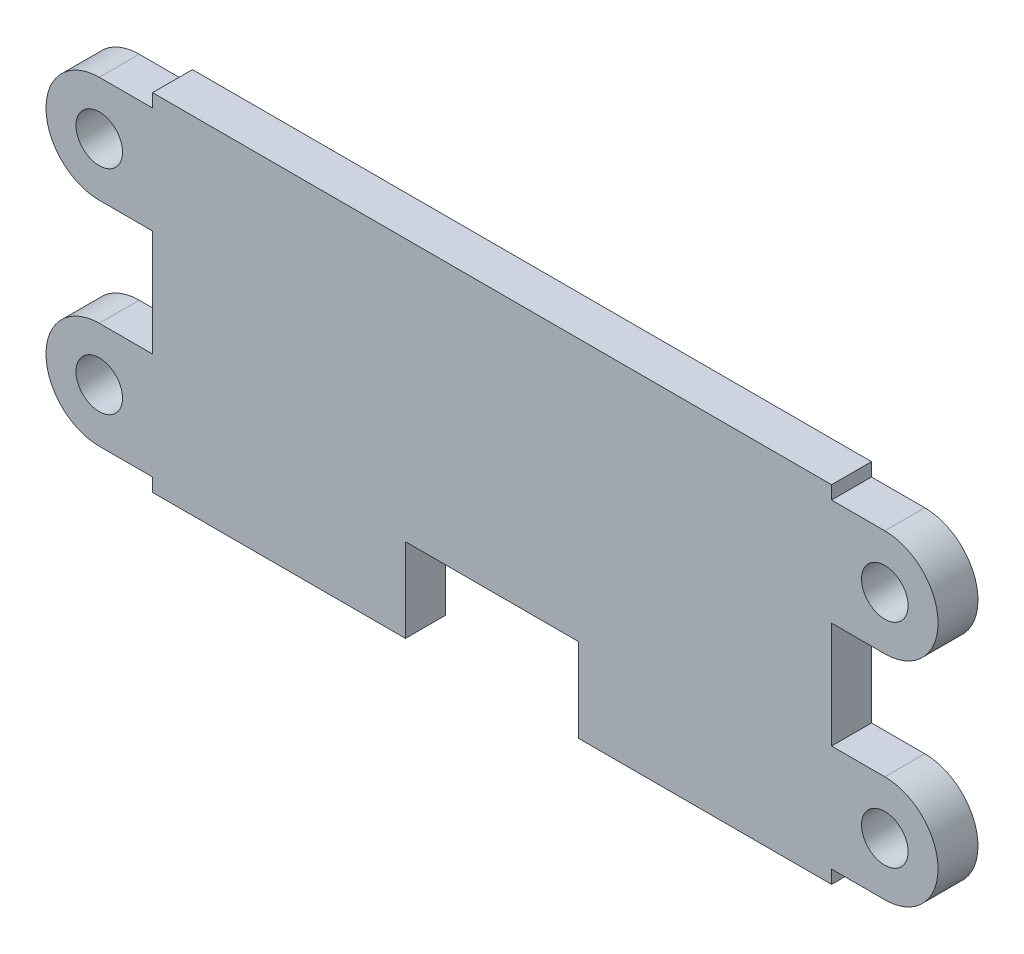
SolidWorks part; units mm, degrees
ref_plane "Ebene vorne" through (0, 0, 0) normal (0, 0, 1) x (1, 0, 0)
ref_plane "Ebene oben" through (0, 0, 0) normal (0, 1, 0) x (1, 0, 0)
ref_plane "Ebene rechts" through (0, 0, 0) normal (1, 0, 0) x (0, 0, -1)
sketch "Skizze1" plane through (0, 0, 0) normal (0, 0, 1) x (1, 0, 0)
  line L16 (-551.7525, 213.3432) -> (-551.7525, 212.3432)
  line L17 (-551.7525, 212.3432) -> (-555.7525, 212.3432)
  line L18 (-555.7525, 204.3432) -> (-551.7525, 204.3432)
  line L19 (-551.7525, 204.3432) -> (-551.7525, 196.3432)
  line L20 (-551.7525, 196.3432) -> (-555.7525, 196.3432)
  line L21 (-555.7525, 188.3432) -> (-551.7525, 188.3432)
  line L22 (-551.7525, 188.3432) -> (-551.7525, 187.3432)
  line L23 (-551.7525, 187.3432) -> (-532.7525, 187.3432)
  line L24 (-500.7525, 187.3432) -> (-500.7525, 188.3432)
  line L25 (-500.7525, 188.3432) -> (-496.7525, 188.3432)
  line L26 (-496.7525, 196.3432) -> (-500.7525, 196.3432)
  line L27 (-500.7525, 196.3432) -> (-500.7525, 204.3432)
  line L28 (-500.7525, 204.3432) -> (-496.7525, 204.3432)
  line L29 (-496.7525, 212.3432) -> (-500.7525, 212.3432)
  line L30 (-500.7525, 212.3432) -> (-500.7525, 213.3432)
  line L31 (-500.7525, 213.3432) -> (-551.7525, 213.3432)
  line L32 (-551.7525, 213.3432) -> (-551.7525, 212.3432)
  line L33 (-551.7525, 212.3432) -> (-555.7525, 212.3432)
  line L34 (-555.7525, 204.3432) -> (-551.7525, 204.3432)
  line L35 (-551.7525, 204.3432) -> (-551.7525, 196.3432)
  line L36 (-551.7525, 196.3432) -> (-555.7525, 196.3432)
  line L37 (-555.7525, 188.3432) -> (-551.7525, 188.3432)
  line L38 (-551.7525, 188.3432) -> (-551.7525, 187.3432)
  line L39 (-551.7525, 187.3432) -> (-532.7525, 187.3432)
  line L40 (-500.7525, 187.3432) -> (-500.7525, 188.3432)
  line L41 (-500.7525, 188.3432) -> (-496.7525, 188.3432)
  line L42 (-496.7525, 196.3432) -> (-500.7525, 196.3432)
  line L43 (-500.7525, 196.3432) -> (-500.7525, 204.3432)
  line L44 (-500.7525, 204.3432) -> (-496.7525, 204.3432)
  line L45 (-496.7525, 212.3432) -> (-500.7525, 212.3432)
  line L46 (-500.7525, 212.3432) -> (-500.7525, 213.3432)
  line L47 (-500.7525, 213.3432) -> (-551.7525, 213.3432)
  line L120 (-532.7525, 187.3432) -> (-532.7525, 193.635)
  line L121 (-532.7525, 193.635) -> (-519.7525, 193.635)
  line L122 (-519.7525, 193.635) -> (-519.7525, 187.3432)
  line L128 (-502.7525, 189.3432) -> (-519.7525, 189.3432)
  line L130 (-519.7525, 189.3432) -> (-519.7525, 187.3432)
  line L132 (-519.7525, 187.3432) -> (-500.7525, 187.3432)
  line L133 (-519.7525, 187.3432) -> (-500.7525, 187.3432)
  line L134 (-532.7525, 187.3432) -> (-532.7525, 189.3432)
  line L136 (-532.7525, 189.3432) -> (-549.7525, 189.3432)
  line L138 (-549.7525, 189.3432) -> (-549.7525, 211.3432)
  line L140 (-549.7525, 211.3432) -> (-502.7525, 211.3432)
  line L142 (-502.7525, 211.3432) -> (-502.7525, 189.3432)
  arc A4 (-555.7525, 212.3432) -> (-555.7525, 204.3432) centre (-555.7525, 208.3432) ccw
  arc A5 (-555.7525, 196.3432) -> (-555.7525, 188.3432) centre (-555.7525, 192.3432) ccw
  arc A6 (-496.7525, 188.3432) -> (-496.7525, 196.3432) centre (-496.7525, 192.3432) ccw
  arc A7 (-496.7525, 204.3432) -> (-496.7525, 212.3432) centre (-496.7525, 208.3432) ccw
  arc A8 (-555.7525, 212.3432) -> (-555.7525, 204.3432) centre (-555.7525, 208.3432) ccw
  arc A9 (-555.7525, 196.3432) -> (-555.7525, 188.3432) centre (-555.7525, 192.3432) ccw
  arc A10 (-496.7525, 188.3432) -> (-496.7525, 196.3432) centre (-496.7525, 192.3432) ccw
  arc A11 (-496.7525, 204.3432) -> (-496.7525, 212.3432) centre (-496.7525, 208.3432) ccw
  circle A28 centre (-538.7525, 200.3432) radius 9 construction
  dimension "D1" = 0
extrude "Aufsatz-Linear austragen1" add sketch "Skizze1" along normal blind 3 contours A8 L34 L35 L36 A9 L37 L38 L39 L120 L121 L122 L133 L40 L41 A10 L42 L43 L44 A11 L45 L46 L47 L32 L33
hole_wizard "Ø3.5 (3.5) Durchmesser Bohrung1" positions "Skizze4" profile "Skizze5" hole size "Ø3.5" standard "ISO" end condition up to next
sketch "Skizze4" plane through (0, 0, 3) normal (0, 0, 1) x (1, 0, 0)
  point P0 (-555.7525, 208.3432)
  point P3 (-555.7525, 192.3432)
  point P6 (-496.7525, 192.3432)
  point P9 (-496.7525, 208.3432)
sketch "Skizze5" plane through (-555.7525, 208.3432, 3) normal (1, 0, 0) x (0, -1, 0)
  line L0 (0, 0) -> (0, 3)
  line L1 (0, 3) -> (1.75, 3)
  line L2 (1.75, 3) -> (1.75, 0)
  line L5 (1.75, 0) -> (0, 0)
  line L11 (0, -6.35) -> (0, 107.95) construction
  dimension "Bohrerdurchmesser" = 3.5
  dimension "Bohrungstiefe" = 3
sketch "Skizze6" plane through (0, 0, 3) normal (0, 0, 1) x (1, 0, 0)
  line L0 (-526.2525, 213.3432) -> (-526.2525, 179.3188) construction
  line L1 (-500.7525, 213.3432) -> (-551.7525, 213.3432) construction
  line L2 (-551.7525, 187.3432) -> (-532.7525, 187.3432) construction
  line L3 (-532.7525, 187.3432) -> (-519.7525, 187.3432)
  line L4 (-532.7525, 187.3432) -> (-532.7525, 193.3432)
  line L5 (-532.7525, 193.3432) -> (-519.7525, 193.3432)
  line L6 (-519.7525, 187.3432) -> (-519.7525, 193.3432)
  dimension "D1" = 13
  dimension "D2" = 6
